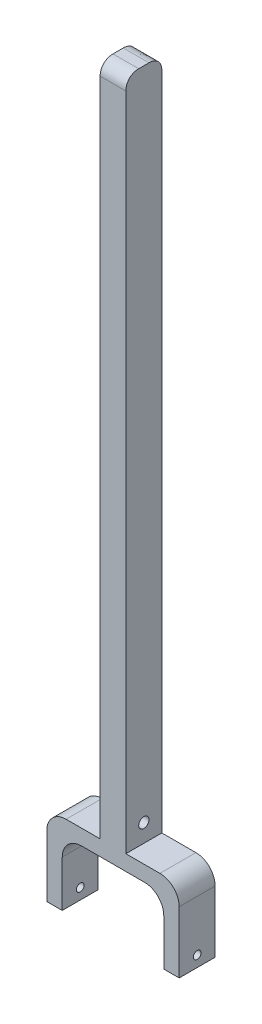
SolidWorks part; units mm, degrees
ref_plane "Plan de face" through (0, 0, 0) normal (0, 0, 1) x (1, 0, 0)
ref_plane "Plan de dessus" through (0, 0, 0) normal (0, 1, 0) x (1, 0, 0)
ref_plane "Plan de droite" through (0, 0, 0) normal (1, 0, 0) x (0, 0, -1)
sketch "Esquisse1" plane through (0, 0, 0) normal (0, 0, 1) x (1, 0, 0)
  line L0 (51.5, 0) -> (51.5, 63) construction
  line L1 (0, 0) -> (103, 0)
  line L2 (0, 0) -> (0, 48)
  line L3 (15, 63) -> (88, 63)
  line L4 (103, 0) -> (103, 48)
  line L5 (12, 0) -> (91, 0)
  line L6 (12, 0) -> (12, 36)
  line L7 (27, 51) -> (76, 51)
  line L8 (91, 0) -> (91, 36)
  arc A0 (0, 48) -> (15, 63) centre (15, 48) cw
  arc A1 (103, 48) -> (88, 63) centre (88, 48) ccw
  arc A2 (76, 51) -> (91, 36) centre (76, 36) cw
  arc A3 (12, 36) -> (27, 51) centre (27, 36) cw
  point P11 (51.5, 51)
  dimension "D4" = 15
  dimension "D1" = 63
  dimension "D2" = 79
  dimension "D3" = 12
  dimension "D5" = 12
extrude "Boss.-Extru.1" add sketch "Esquisse1" along normal blind 28 contours L7 L0 L3 A0 L2 L1 L6 A3 | L0 L7 A2 L8 L1 L4 A1 L3 region at (39.25, 51.8137, 0) region at (52.3137, 57, 0)
sketch "Esquisse2" plane through (103, 0, 0) normal (1, 0, 0) x (0, 0, -1)
  line L0 (-28, 0) -> (0, 0) construction
  circle A0 centre (-14, 8.5) radius 3
  point P4 (-14, 0)
  dimension "D1" = 6
  dimension "D2" = 8.5
extrude "Enlèv. mat.-Extru.1" cut sketch "Esquisse2" against normal through all
sketch "Esquisse3" plane through (0, 63, 0) normal (0, 1, 0) x (1, 0, 0)
  line L0 (15, 0) -> (88, 0) construction
  line L1 (41.5, 0) -> (61.5, 0)
  line L2 (41.5, 0) -> (41.5, -28)
  line L3 (41.5, -28) -> (61.5, -28)
  line L4 (61.5, 0) -> (61.5, -28)
  line L5 (15, -28) -> (88, -28) construction
  line L6 (51.5, 0) -> (51.5, -28) construction
  point P10 (51.5, 0)
  dimension "D1" = 20
extrude "Boss.-Extru.2" add sketch "Esquisse3" along normal blind 524
fillet "Congé1" radius 10 2 edges at (51.5, 587, 0) (51.5, 587, 28) conic radius 9
sketch "Esquisse4" plane through (41.5, 0, 0) normal (-1, 0, 0) x (0, 0, 1)
  line L0 (10, 587) -> (18, 587) construction
  line L1 (14, 587) -> (14, 67.2523) construction
  line L2 (0, 63) -> (28, 63) construction
  circle A0 centre (14, 77) radius 4
  dimension "D1" = 14
  dimension "D2" = 8
extrude "Enlèv. mat.-Extru.2" cut sketch "Esquisse4" against normal through all
